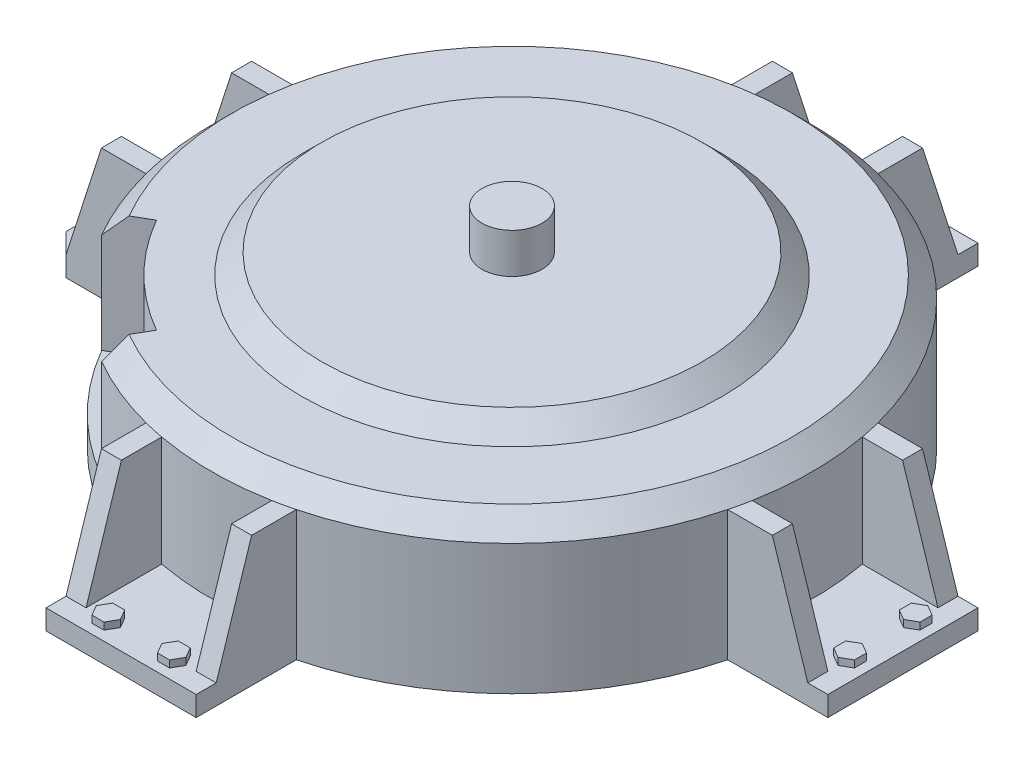
SolidWorks part; units mm, degrees
ref_plane "Front Plane" through (0, 0, 0) normal (0, 0, 1) x (1, 0, 0)
ref_plane "Top Plane" through (0, 0, 0) normal (0, 1, 0) x (1, 0, 0)
ref_plane "Right Plane" through (0, 0, 0) normal (1, 0, 0) x (0, 0, -1)
sketch "Sketch1" plane through (0, 0, 0) normal (0, 1, 0) x (1, 0, 0)
  circle A0 centre (0, 0) radius 150
extrude "Boss-Extrude1" add sketch "Sketch1" along normal blind 75
chamfer "Chamfer1" distance 10 angle 45 1 edges at (0, 75, 150)
sketch "Sketch4" plane through (0, 0, 0) normal (0, -1, 0) x (1, 0, 0)
  line L1 (-195.2369, 37.5) -> (-145.2369, 37.5)
  line L2 (-195.2369, 37.5) -> (-195.2369, -37.5)
  line L3 (-195.2369, -37.5) -> (-145.2369, -37.5)
  circle A0 centre (0, 0) radius 150 construction
  circle A1 centre (0, 0) radius 150
  point P0 (-150, 0)
  circle M5 centre (0, 0) radius 150
  dimension "D1" = 50
  dimension "D2" = 75
extrude "Boss-Extrude2" add sketch "Sketch4" against normal blind 10 contours L2 L3 L1 M5 region at (-171.8083, 0, 0)
chamfer "Chamfer2" distance 10 angle 45 2 edges at (-195.2369, 5, 37.5) (-195.2369, 5, -37.5)
sketch "Sketch5" plane through (0, 0, 37.5) normal (0, 0, 1) x (1, 0, 0)
  line L0 (-145.2369, 10) -> (-145.2369, 65)
  line L1 (-150, 65) -> (150, 65) construction
  line L2 (-145.2369, 65) -> (-167.5569, 65)
  line L3 (-167.5569, 65) -> (-185.2369, 10)
  line L4 (-185.2369, 10) -> (-145.2369, 10)
  line L5 (-185.2369, 10) -> (-185.2369, 0) construction
  line L6 (-185.2369, 10) -> (-145.2369, 10) construction
  dimension "D1" = 17.68
extrude "Boss-Extrude3" add sketch "Sketch5" against normal blind 10
sketch "Sketch6" plane through (0, 10, 0) normal (0, 1, 0) x (1, 0, 0)
  line L0 (-185.2369, 37.5) -> (-185.2369, -55.4341) construction
  line L2 (-185.2369, -10.3772) -> (-190.433, -13.3772)
  line L3 (-190.433, -13.3772) -> (-190.433, -19.3772)
  line L4 (-190.433, -19.3772) -> (-185.2369, -22.3772)
  line L5 (-185.2369, -22.3772) -> (-180.0407, -19.3772)
  line L6 (-180.0407, -19.3772) -> (-180.0407, -13.3772)
  line L7 (-180.0407, -13.3772) -> (-185.2369, -10.3772)
  circle A0 centre (-185.2369, -16.3772) radius 5.1962 construction
  dimension "D1" = 6
extrude "Boss-Extrude4" add sketch "Sketch6" along normal blind 3.5
mirror "Mirror1" about plane through (0, 0, 0) normal (0, 0, 1) of "Boss-Extrude3", "Boss-Extrude4"
pattern_circular "CirPattern1" count 4 over 360 about axis through (0, 0, 0) along (0, 1, 0) of "Boss-Extrude3", "Boss-Extrude2", "Mirror1"
sketch "Sketch7" plane through (0, 75, 0) normal (0, 1, 0) x (1, 0, 0)
  line L2 (-112.5833, -65) -> (-129.9038, -75)
  line L3 (-65, -112.5833) -> (-75, -129.9038)
  arc A0 (-112.5833, -65) -> (-65, -112.5833) centre (0, 0) ccw
  arc A1 (-145.2369, -37.5) -> (-37.5, -145.2369) centre (0, 0) ccw construction
  arc A2 (-129.9038, -75) -> (-75, -129.9038) centre (0, 0) ccw
extrude "Cut-Extrude1" cut sketch "Sketch7" against normal blind 60
sketch "Sketch8" plane through (0, 75, 0) normal (0, 1, 0) x (1, 0, 0)
  circle A0 centre (0, 0) radius 110
extrude "Boss-Extrude5" add sketch "Sketch8" along normal blind 10
chamfer "Chamfer3" distance 15 angle 45 1 edges at (0, 85, 110)
sketch "Sketch9" plane through (0, 85, 0) normal (0, 1, 0) x (1, 0, 0)
  circle A0 centre (0, 0) radius 15
extrude "Boss-Extrude6" add sketch "Sketch9" along normal blind 20
